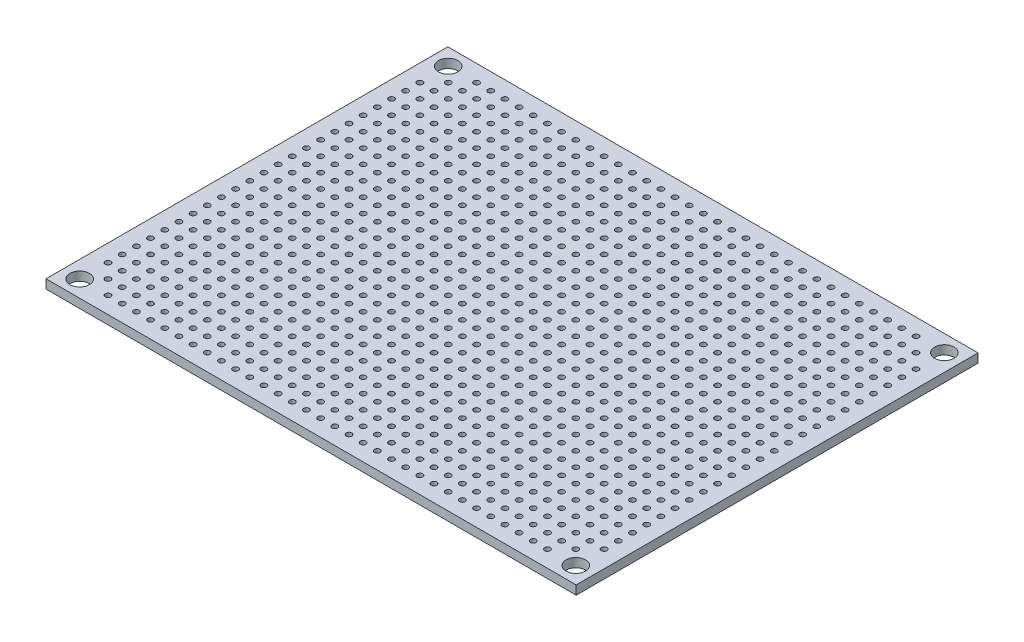
SolidWorks part; units mm, degrees
ref_plane "正面" through (0, 0, 0) normal (0, 0, 1) x (1, 0, 0)
ref_plane "平面" through (0, 0, 0) normal (0, 1, 0) x (1, 0, 0)
ref_plane "右側面" through (0, 0, 0) normal (1, 0, 0) x (0, 0, -1)
sketch "ｽｹｯﾁ1" plane through (0, 0, 0) normal (0, 1, 0) x (1, 0, 0)
  line L1 (0, 0) -> (95, 0)
  line L2 (0, 0) -> (0, 72)
  line L3 (0, 72) -> (95, 72)
  line L4 (95, 0) -> (95, 72)
  line L5 (3.05, 69.02) -> (91.95, 69.02) construction
  line L6 (3.05, 69.02) -> (3.05, 2.98) construction
  line L7 (3.05, 2.98) -> (91.95, 2.98) construction
  line L8 (91.95, 69.02) -> (91.95, 2.98) construction
  circle A0 centre (3.05, 69.02) radius 1.75
  circle A1 centre (91.95, 69.02) radius 1.75
  circle A2 centre (91.95, 2.98) radius 1.75
  circle A3 centre (3.05, 2.98) radius 1.75
  circle A5 centre (5.59, 69.02) radius 0.5
  circle A6 centre (8.13, 69.02) radius 0.5
  circle A7 centre (10.67, 69.02) radius 0.5
  circle A8 centre (13.21, 69.02) radius 0.5
  circle A9 centre (15.75, 69.02) radius 0.5
  circle A10 centre (18.29, 69.02) radius 0.5
  circle A11 centre (20.83, 69.02) radius 0.5
  circle A12 centre (23.37, 69.02) radius 0.5
  circle A13 centre (25.91, 69.02) radius 0.5
  circle A14 centre (28.45, 69.02) radius 0.5
  circle A15 centre (30.99, 69.02) radius 0.5
  circle A16 centre (33.53, 69.02) radius 0.5
  circle A17 centre (36.07, 69.02) radius 0.5
  circle A18 centre (38.61, 69.02) radius 0.5
  circle A19 centre (41.15, 69.02) radius 0.5
  circle A20 centre (43.69, 69.02) radius 0.5
  circle A21 centre (46.23, 69.02) radius 0.5
  circle A22 centre (48.77, 69.02) radius 0.5
  circle A23 centre (51.31, 69.02) radius 0.5
  circle A24 centre (53.85, 69.02) radius 0.5
  circle A25 centre (56.39, 69.02) radius 0.5
  circle A26 centre (58.93, 69.02) radius 0.5
  circle A27 centre (61.47, 69.02) radius 0.5
  circle A28 centre (64.01, 69.02) radius 0.5
  circle A29 centre (66.55, 69.02) radius 0.5
  circle A30 centre (69.09, 69.02) radius 0.5
  circle A31 centre (71.63, 69.02) radius 0.5
  circle A32 centre (74.17, 69.02) radius 0.5
  circle A33 centre (76.71, 69.02) radius 0.5
  circle A34 centre (79.25, 69.02) radius 0.5
  circle A35 centre (81.79, 69.02) radius 0.5
  circle A36 centre (84.33, 69.02) radius 0.5
  circle A37 centre (86.87, 69.02) radius 0.5
  circle A38 centre (89.41, 69.02) radius 0.5
  circle A39 centre (91.95, 69.02) radius 0.5
  circle A40 centre (3.05, 66.48) radius 0.5
  circle A41 centre (5.59, 66.48) radius 0.5
  circle A42 centre (8.13, 66.48) radius 0.5
  circle A43 centre (10.67, 66.48) radius 0.5
  circle A44 centre (13.21, 66.48) radius 0.5
  circle A45 centre (15.75, 66.48) radius 0.5
  circle A46 centre (18.29, 66.48) radius 0.5
  circle A47 centre (20.83, 66.48) radius 0.5
  circle A48 centre (23.37, 66.48) radius 0.5
  circle A49 centre (25.91, 66.48) radius 0.5
  circle A50 centre (28.45, 66.48) radius 0.5
  circle A51 centre (30.99, 66.48) radius 0.5
  circle A52 centre (33.53, 66.48) radius 0.5
  circle A53 centre (36.07, 66.48) radius 0.5
  circle A54 centre (38.61, 66.48) radius 0.5
  circle A55 centre (41.15, 66.48) radius 0.5
  circle A56 centre (43.69, 66.48) radius 0.5
  circle A57 centre (46.23, 66.48) radius 0.5
  circle A58 centre (48.77, 66.48) radius 0.5
  circle A59 centre (51.31, 66.48) radius 0.5
  circle A60 centre (53.85, 66.48) radius 0.5
  circle A61 centre (56.39, 66.48) radius 0.5
  circle A62 centre (58.93, 66.48) radius 0.5
  circle A63 centre (61.47, 66.48) radius 0.5
  circle A64 centre (64.01, 66.48) radius 0.5
  circle A65 centre (66.55, 66.48) radius 0.5
  circle A66 centre (69.09, 66.48) radius 0.5
  circle A67 centre (71.63, 66.48) radius 0.5
  circle A68 centre (74.17, 66.48) radius 0.5
  circle A69 centre (76.71, 66.48) radius 0.5
  circle A70 centre (79.25, 66.48) radius 0.5
  circle A71 centre (81.79, 66.48) radius 0.5
  circle A72 centre (84.33, 66.48) radius 0.5
  circle A73 centre (86.87, 66.48) radius 0.5
  circle A74 centre (89.41, 66.48) radius 0.5
  circle A75 centre (91.95, 66.48) radius 0.5
  circle A76 centre (3.05, 63.94) radius 0.5
  circle A77 centre (5.59, 63.94) radius 0.5
  circle A78 centre (8.13, 63.94) radius 0.5
  circle A79 centre (10.67, 63.94) radius 0.5
  circle A80 centre (13.21, 63.94) radius 0.5
  circle A81 centre (15.75, 63.94) radius 0.5
  circle A82 centre (18.29, 63.94) radius 0.5
  circle A83 centre (20.83, 63.94) radius 0.5
  circle A84 centre (23.37, 63.94) radius 0.5
  circle A85 centre (25.91, 63.94) radius 0.5
  circle A86 centre (28.45, 63.94) radius 0.5
  circle A87 centre (30.99, 63.94) radius 0.5
  circle A88 centre (33.53, 63.94) radius 0.5
  circle A89 centre (36.07, 63.94) radius 0.5
  circle A90 centre (38.61, 63.94) radius 0.5
  circle A91 centre (41.15, 63.94) radius 0.5
  circle A92 centre (43.69, 63.94) radius 0.5
  circle A93 centre (46.23, 63.94) radius 0.5
  circle A94 centre (48.77, 63.94) radius 0.5
  circle A95 centre (51.31, 63.94) radius 0.5
  circle A96 centre (53.85, 63.94) radius 0.5
  circle A97 centre (56.39, 63.94) radius 0.5
  circle A98 centre (58.93, 63.94) radius 0.5
  circle A99 centre (61.47, 63.94) radius 0.5
  circle A100 centre (64.01, 63.94) radius 0.5
  circle A101 centre (66.55, 63.94) radius 0.5
  circle A102 centre (69.09, 63.94) radius 0.5
  circle A103 centre (71.63, 63.94) radius 0.5
  circle A104 centre (74.17, 63.94) radius 0.5
  circle A105 centre (76.71, 63.94) radius 0.5
  circle A106 centre (79.25, 63.94) radius 0.5
  circle A107 centre (81.79, 63.94) radius 0.5
  circle A108 centre (84.33, 63.94) radius 0.5
  circle A109 centre (86.87, 63.94) radius 0.5
  circle A110 centre (89.41, 63.94) radius 0.5
  circle A111 centre (91.95, 63.94) radius 0.5
  circle A112 centre (3.05, 61.4) radius 0.5
  circle A113 centre (5.59, 61.4) radius 0.5
  circle A114 centre (8.13, 61.4) radius 0.5
  circle A115 centre (10.67, 61.4) radius 0.5
  circle A116 centre (13.21, 61.4) radius 0.5
  circle A117 centre (15.75, 61.4) radius 0.5
  circle A118 centre (18.29, 61.4) radius 0.5
  circle A119 centre (20.83, 61.4) radius 0.5
  circle A120 centre (23.37, 61.4) radius 0.5
  circle A121 centre (25.91, 61.4) radius 0.5
  circle A122 centre (28.45, 61.4) radius 0.5
  circle A123 centre (30.99, 61.4) radius 0.5
  circle A124 centre (33.53, 61.4) radius 0.5
  circle A125 centre (36.07, 61.4) radius 0.5
  circle A126 centre (38.61, 61.4) radius 0.5
  circle A127 centre (41.15, 61.4) radius 0.5
  circle A128 centre (43.69, 61.4) radius 0.5
  circle A129 centre (46.23, 61.4) radius 0.5
  circle A130 centre (48.77, 61.4) radius 0.5
  circle A131 centre (51.31, 61.4) radius 0.5
  circle A132 centre (53.85, 61.4) radius 0.5
  circle A133 centre (56.39, 61.4) radius 0.5
  circle A134 centre (58.93, 61.4) radius 0.5
  circle A135 centre (61.47, 61.4) radius 0.5
  circle A136 centre (64.01, 61.4) radius 0.5
  circle A137 centre (66.55, 61.4) radius 0.5
  circle A138 centre (69.09, 61.4) radius 0.5
  circle A139 centre (71.63, 61.4) radius 0.5
  circle A140 centre (74.17, 61.4) radius 0.5
  circle A141 centre (76.71, 61.4) radius 0.5
  circle A142 centre (79.25, 61.4) radius 0.5
  circle A143 centre (81.79, 61.4) radius 0.5
  circle A144 centre (84.33, 61.4) radius 0.5
  circle A145 centre (86.87, 61.4) radius 0.5
  circle A146 centre (89.41, 61.4) radius 0.5
  circle A147 centre (91.95, 61.4) radius 0.5
  circle A148 centre (3.05, 58.86) radius 0.5
  circle A149 centre (5.59, 58.86) radius 0.5
  circle A150 centre (8.13, 58.86) radius 0.5
  circle A151 centre (10.67, 58.86) radius 0.5
  circle A152 centre (13.21, 58.86) radius 0.5
  circle A153 centre (15.75, 58.86) radius 0.5
  circle A154 centre (18.29, 58.86) radius 0.5
  circle A155 centre (20.83, 58.86) radius 0.5
  circle A156 centre (23.37, 58.86) radius 0.5
  circle A157 centre (25.91, 58.86) radius 0.5
  circle A158 centre (28.45, 58.86) radius 0.5
  circle A159 centre (30.99, 58.86) radius 0.5
  circle A160 centre (33.53, 58.86) radius 0.5
  circle A161 centre (36.07, 58.86) radius 0.5
  circle A162 centre (38.61, 58.86) radius 0.5
  circle A163 centre (41.15, 58.86) radius 0.5
  circle A164 centre (43.69, 58.86) radius 0.5
  circle A165 centre (46.23, 58.86) radius 0.5
  circle A166 centre (48.77, 58.86) radius 0.5
  circle A167 centre (51.31, 58.86) radius 0.5
  circle A168 centre (53.85, 58.86) radius 0.5
  circle A169 centre (56.39, 58.86) radius 0.5
  circle A170 centre (58.93, 58.86) radius 0.5
  circle A171 centre (61.47, 58.86) radius 0.5
  circle A172 centre (64.01, 58.86) radius 0.5
  circle A173 centre (66.55, 58.86) radius 0.5
  circle A174 centre (69.09, 58.86) radius 0.5
  circle A175 centre (71.63, 58.86) radius 0.5
  circle A176 centre (74.17, 58.86) radius 0.5
  circle A177 centre (76.71, 58.86) radius 0.5
  circle A178 centre (79.25, 58.86) radius 0.5
  circle A179 centre (81.79, 58.86) radius 0.5
  circle A180 centre (84.33, 58.86) radius 0.5
  circle A181 centre (86.87, 58.86) radius 0.5
  circle A182 centre (89.41, 58.86) radius 0.5
  circle A183 centre (91.95, 58.86) radius 0.5
  circle A184 centre (3.05, 56.32) radius 0.5
  circle A185 centre (5.59, 56.32) radius 0.5
  circle A186 centre (8.13, 56.32) radius 0.5
  circle A187 centre (10.67, 56.32) radius 0.5
  circle A188 centre (13.21, 56.32) radius 0.5
  circle A189 centre (15.75, 56.32) radius 0.5
  circle A190 centre (18.29, 56.32) radius 0.5
  circle A191 centre (20.83, 56.32) radius 0.5
  circle A192 centre (23.37, 56.32) radius 0.5
  circle A193 centre (25.91, 56.32) radius 0.5
  circle A194 centre (28.45, 56.32) radius 0.5
  circle A195 centre (30.99, 56.32) radius 0.5
  circle A196 centre (33.53, 56.32) radius 0.5
  circle A197 centre (36.07, 56.32) radius 0.5
  circle A198 centre (38.61, 56.32) radius 0.5
  circle A199 centre (41.15, 56.32) radius 0.5
  circle A200 centre (43.69, 56.32) radius 0.5
  circle A201 centre (46.23, 56.32) radius 0.5
  circle A202 centre (48.77, 56.32) radius 0.5
  circle A203 centre (51.31, 56.32) radius 0.5
  circle A204 centre (53.85, 56.32) radius 0.5
  circle A205 centre (56.39, 56.32) radius 0.5
  circle A206 centre (58.93, 56.32) radius 0.5
  circle A207 centre (61.47, 56.32) radius 0.5
  circle A208 centre (64.01, 56.32) radius 0.5
  circle A209 centre (66.55, 56.32) radius 0.5
  circle A210 centre (69.09, 56.32) radius 0.5
  circle A211 centre (71.63, 56.32) radius 0.5
  circle A212 centre (74.17, 56.32) radius 0.5
  circle A213 centre (76.71, 56.32) radius 0.5
  circle A214 centre (79.25, 56.32) radius 0.5
  circle A215 centre (81.79, 56.32) radius 0.5
  circle A216 centre (84.33, 56.32) radius 0.5
  circle A217 centre (86.87, 56.32) radius 0.5
  circle A218 centre (89.41, 56.32) radius 0.5
  circle A219 centre (91.95, 56.32) radius 0.5
  circle A220 centre (3.05, 53.78) radius 0.5
  circle A221 centre (5.59, 53.78) radius 0.5
  circle A222 centre (8.13, 53.78) radius 0.5
  circle A223 centre (10.67, 53.78) radius 0.5
  circle A224 centre (13.21, 53.78) radius 0.5
  circle A225 centre (15.75, 53.78) radius 0.5
  circle A226 centre (18.29, 53.78) radius 0.5
  circle A227 centre (20.83, 53.78) radius 0.5
  circle A228 centre (23.37, 53.78) radius 0.5
  circle A229 centre (25.91, 53.78) radius 0.5
  circle A230 centre (28.45, 53.78) radius 0.5
  circle A231 centre (30.99, 53.78) radius 0.5
  circle A232 centre (33.53, 53.78) radius 0.5
  circle A233 centre (36.07, 53.78) radius 0.5
  circle A234 centre (38.61, 53.78) radius 0.5
  circle A235 centre (41.15, 53.78) radius 0.5
  circle A236 centre (43.69, 53.78) radius 0.5
  circle A237 centre (46.23, 53.78) radius 0.5
  circle A238 centre (48.77, 53.78) radius 0.5
  circle A239 centre (51.31, 53.78) radius 0.5
  circle A240 centre (53.85, 53.78) radius 0.5
  circle A241 centre (56.39, 53.78) radius 0.5
  circle A242 centre (58.93, 53.78) radius 0.5
  circle A243 centre (61.47, 53.78) radius 0.5
  circle A244 centre (64.01, 53.78) radius 0.5
  circle A245 centre (66.55, 53.78) radius 0.5
  circle A246 centre (69.09, 53.78) radius 0.5
  circle A247 centre (71.63, 53.78) radius 0.5
  circle A248 centre (74.17, 53.78) radius 0.5
  circle A249 centre (76.71, 53.78) radius 0.5
  circle A250 centre (79.25, 53.78) radius 0.5
  circle A251 centre (81.79, 53.78) radius 0.5
  circle A252 centre (84.33, 53.78) radius 0.5
  circle A253 centre (86.87, 53.78) radius 0.5
  circle A254 centre (89.41, 53.78) radius 0.5
  circle A255 centre (91.95, 53.78) radius 0.5
  circle A256 centre (3.05, 51.24) radius 0.5
  circle A257 centre (5.59, 51.24) radius 0.5
  circle A258 centre (8.13, 51.24) radius 0.5
  circle A259 centre (10.67, 51.24) radius 0.5
  circle A260 centre (13.21, 51.24) radius 0.5
  circle A261 centre (15.75, 51.24) radius 0.5
  circle A262 centre (18.29, 51.24) radius 0.5
  circle A263 centre (20.83, 51.24) radius 0.5
  circle A264 centre (23.37, 51.24) radius 0.5
  circle A265 centre (25.91, 51.24) radius 0.5
  circle A266 centre (28.45, 51.24) radius 0.5
  circle A267 centre (30.99, 51.24) radius 0.5
  circle A268 centre (33.53, 51.24) radius 0.5
  circle A269 centre (36.07, 51.24) radius 0.5
  circle A270 centre (38.61, 51.24) radius 0.5
  circle A271 centre (41.15, 51.24) radius 0.5
  circle A272 centre (43.69, 51.24) radius 0.5
  circle A273 centre (46.23, 51.24) radius 0.5
  circle A274 centre (48.77, 51.24) radius 0.5
  circle A275 centre (51.31, 51.24) radius 0.5
  circle A276 centre (53.85, 51.24) radius 0.5
  circle A277 centre (56.39, 51.24) radius 0.5
  circle A278 centre (58.93, 51.24) radius 0.5
  circle A279 centre (61.47, 51.24) radius 0.5
  circle A280 centre (64.01, 51.24) radius 0.5
  circle A281 centre (66.55, 51.24) radius 0.5
  circle A282 centre (69.09, 51.24) radius 0.5
  circle A283 centre (71.63, 51.24) radius 0.5
  circle A284 centre (74.17, 51.24) radius 0.5
  circle A285 centre (76.71, 51.24) radius 0.5
  circle A286 centre (79.25, 51.24) radius 0.5
  circle A287 centre (81.79, 51.24) radius 0.5
  circle A288 centre (84.33, 51.24) radius 0.5
  circle A289 centre (86.87, 51.24) radius 0.5
  circle A290 centre (89.41, 51.24) radius 0.5
  circle A291 centre (91.95, 51.24) radius 0.5
  circle A292 centre (3.05, 48.7) radius 0.5
  circle A293 centre (5.59, 48.7) radius 0.5
  circle A294 centre (8.13, 48.7) radius 0.5
  circle A295 centre (10.67, 48.7) radius 0.5
  circle A296 centre (13.21, 48.7) radius 0.5
  circle A297 centre (15.75, 48.7) radius 0.5
  circle A298 centre (18.29, 48.7) radius 0.5
  circle A299 centre (20.83, 48.7) radius 0.5
  circle A300 centre (23.37, 48.7) radius 0.5
  circle A301 centre (25.91, 48.7) radius 0.5
  circle A302 centre (28.45, 48.7) radius 0.5
  circle A303 centre (30.99, 48.7) radius 0.5
  circle A304 centre (33.53, 48.7) radius 0.5
  circle A305 centre (36.07, 48.7) radius 0.5
  circle A306 centre (38.61, 48.7) radius 0.5
  circle A307 centre (41.15, 48.7) radius 0.5
  circle A308 centre (43.69, 48.7) radius 0.5
  circle A309 centre (46.23, 48.7) radius 0.5
  circle A310 centre (48.77, 48.7) radius 0.5
  circle A311 centre (51.31, 48.7) radius 0.5
  circle A312 centre (53.85, 48.7) radius 0.5
  circle A313 centre (56.39, 48.7) radius 0.5
  circle A314 centre (58.93, 48.7) radius 0.5
  circle A315 centre (61.47, 48.7) radius 0.5
  circle A316 centre (64.01, 48.7) radius 0.5
  circle A317 centre (66.55, 48.7) radius 0.5
  circle A318 centre (69.09, 48.7) radius 0.5
  circle A319 centre (71.63, 48.7) radius 0.5
  circle A320 centre (74.17, 48.7) radius 0.5
  circle A321 centre (76.71, 48.7) radius 0.5
  circle A322 centre (79.25, 48.7) radius 0.5
  circle A323 centre (81.79, 48.7) radius 0.5
  circle A324 centre (84.33, 48.7) radius 0.5
  circle A325 centre (86.87, 48.7) radius 0.5
  circle A326 centre (89.41, 48.7) radius 0.5
  circle A327 centre (91.95, 48.7) radius 0.5
  circle A328 centre (3.05, 46.16) radius 0.5
  circle A329 centre (5.59, 46.16) radius 0.5
  circle A330 centre (8.13, 46.16) radius 0.5
  circle A331 centre (10.67, 46.16) radius 0.5
  circle A332 centre (13.21, 46.16) radius 0.5
  circle A333 centre (15.75, 46.16) radius 0.5
  circle A334 centre (18.29, 46.16) radius 0.5
  circle A335 centre (20.83, 46.16) radius 0.5
  circle A336 centre (23.37, 46.16) radius 0.5
  circle A337 centre (25.91, 46.16) radius 0.5
  circle A338 centre (28.45, 46.16) radius 0.5
  circle A339 centre (30.99, 46.16) radius 0.5
  circle A340 centre (33.53, 46.16) radius 0.5
  circle A341 centre (36.07, 46.16) radius 0.5
  circle A342 centre (38.61, 46.16) radius 0.5
  circle A343 centre (41.15, 46.16) radius 0.5
  circle A344 centre (43.69, 46.16) radius 0.5
  circle A345 centre (46.23, 46.16) radius 0.5
  circle A346 centre (48.77, 46.16) radius 0.5
  circle A347 centre (51.31, 46.16) radius 0.5
  circle A348 centre (53.85, 46.16) radius 0.5
  circle A349 centre (56.39, 46.16) radius 0.5
  circle A350 centre (58.93, 46.16) radius 0.5
  circle A351 centre (61.47, 46.16) radius 0.5
  circle A352 centre (64.01, 46.16) radius 0.5
  circle A353 centre (66.55, 46.16) radius 0.5
  circle A354 centre (69.09, 46.16) radius 0.5
  circle A355 centre (71.63, 46.16) radius 0.5
  circle A356 centre (74.17, 46.16) radius 0.5
  circle A357 centre (76.71, 46.16) radius 0.5
  circle A358 centre (79.25, 46.16) radius 0.5
  circle A359 centre (81.79, 46.16) radius 0.5
  circle A360 centre (84.33, 46.16) radius 0.5
  circle A361 centre (86.87, 46.16) radius 0.5
  circle A362 centre (89.41, 46.16) radius 0.5
  circle A363 centre (91.95, 46.16) radius 0.5
  circle A364 centre (3.05, 43.62) radius 0.5
  circle A365 centre (5.59, 43.62) radius 0.5
  circle A366 centre (8.13, 43.62) radius 0.5
  circle A367 centre (10.67, 43.62) radius 0.5
  circle A368 centre (13.21, 43.62) radius 0.5
  circle A369 centre (15.75, 43.62) radius 0.5
  circle A370 centre (18.29, 43.62) radius 0.5
  circle A371 centre (20.83, 43.62) radius 0.5
  circle A372 centre (23.37, 43.62) radius 0.5
  circle A373 centre (25.91, 43.62) radius 0.5
  circle A374 centre (28.45, 43.62) radius 0.5
  circle A375 centre (30.99, 43.62) radius 0.5
  circle A376 centre (33.53, 43.62) radius 0.5
  circle A377 centre (36.07, 43.62) radius 0.5
  circle A378 centre (38.61, 43.62) radius 0.5
  circle A379 centre (41.15, 43.62) radius 0.5
  circle A380 centre (43.69, 43.62) radius 0.5
  circle A381 centre (46.23, 43.62) radius 0.5
  circle A382 centre (48.77, 43.62) radius 0.5
  circle A383 centre (51.31, 43.62) radius 0.5
  circle A384 centre (53.85, 43.62) radius 0.5
  circle A385 centre (56.39, 43.62) radius 0.5
  circle A386 centre (58.93, 43.62) radius 0.5
  circle A387 centre (61.47, 43.62) radius 0.5
  circle A388 centre (64.01, 43.62) radius 0.5
  circle A389 centre (66.55, 43.62) radius 0.5
  circle A390 centre (69.09, 43.62) radius 0.5
  circle A391 centre (71.63, 43.62) radius 0.5
  circle A392 centre (74.17, 43.62) radius 0.5
  circle A393 centre (76.71, 43.62) radius 0.5
  circle A394 centre (79.25, 43.62) radius 0.5
  circle A395 centre (81.79, 43.62) radius 0.5
  circle A396 centre (84.33, 43.62) radius 0.5
  circle A397 centre (86.87, 43.62) radius 0.5
  circle A398 centre (89.41, 43.62) radius 0.5
  circle A399 centre (91.95, 43.62) radius 0.5
  circle A400 centre (3.05, 41.08) radius 0.5
  circle A401 centre (5.59, 41.08) radius 0.5
  circle A402 centre (8.13, 41.08) radius 0.5
  circle A403 centre (10.67, 41.08) radius 0.5
  circle A404 centre (13.21, 41.08) radius 0.5
  circle A405 centre (15.75, 41.08) radius 0.5
  circle A406 centre (18.29, 41.08) radius 0.5
  circle A407 centre (20.83, 41.08) radius 0.5
  circle A408 centre (23.37, 41.08) radius 0.5
  circle A409 centre (25.91, 41.08) radius 0.5
  circle A410 centre (28.45, 41.08) radius 0.5
  circle A411 centre (30.99, 41.08) radius 0.5
  circle A412 centre (33.53, 41.08) radius 0.5
  circle A413 centre (36.07, 41.08) radius 0.5
  circle A414 centre (38.61, 41.08) radius 0.5
  circle A415 centre (41.15, 41.08) radius 0.5
  circle A416 centre (43.69, 41.08) radius 0.5
  circle A417 centre (46.23, 41.08) radius 0.5
  circle A418 centre (48.77, 41.08) radius 0.5
  circle A419 centre (51.31, 41.08) radius 0.5
  circle A420 centre (53.85, 41.08) radius 0.5
  circle A421 centre (56.39, 41.08) radius 0.5
  circle A422 centre (58.93, 41.08) radius 0.5
  circle A423 centre (61.47, 41.08) radius 0.5
  circle A424 centre (64.01, 41.08) radius 0.5
  circle A425 centre (66.55, 41.08) radius 0.5
  circle A426 centre (69.09, 41.08) radius 0.5
  circle A427 centre (71.63, 41.08) radius 0.5
  circle A428 centre (74.17, 41.08) radius 0.5
  circle A429 centre (76.71, 41.08) radius 0.5
  circle A430 centre (79.25, 41.08) radius 0.5
  circle A431 centre (81.79, 41.08) radius 0.5
  circle A432 centre (84.33, 41.08) radius 0.5
  circle A433 centre (86.87, 41.08) radius 0.5
  circle A434 centre (89.41, 41.08) radius 0.5
  circle A435 centre (91.95, 41.08) radius 0.5
  circle A436 centre (3.05, 38.54) radius 0.5
  circle A437 centre (5.59, 38.54) radius 0.5
  circle A438 centre (8.13, 38.54) radius 0.5
  circle A439 centre (10.67, 38.54) radius 0.5
  circle A440 centre (13.21, 38.54) radius 0.5
  circle A441 centre (15.75, 38.54) radius 0.5
  circle A442 centre (18.29, 38.54) radius 0.5
  circle A443 centre (20.83, 38.54) radius 0.5
  circle A444 centre (23.37, 38.54) radius 0.5
  circle A445 centre (25.91, 38.54) radius 0.5
  circle A446 centre (28.45, 38.54) radius 0.5
  circle A447 centre (30.99, 38.54) radius 0.5
  circle A448 centre (33.53, 38.54) radius 0.5
  circle A449 centre (36.07, 38.54) radius 0.5
  circle A450 centre (38.61, 38.54) radius 0.5
  circle A451 centre (41.15, 38.54) radius 0.5
  circle A452 centre (43.69, 38.54) radius 0.5
  circle A453 centre (46.23, 38.54) radius 0.5
  circle A454 centre (48.77, 38.54) radius 0.5
  circle A455 centre (51.31, 38.54) radius 0.5
  circle A456 centre (53.85, 38.54) radius 0.5
  circle A457 centre (56.39, 38.54) radius 0.5
  circle A458 centre (58.93, 38.54) radius 0.5
  circle A459 centre (61.47, 38.54) radius 0.5
  circle A460 centre (64.01, 38.54) radius 0.5
  circle A461 centre (66.55, 38.54) radius 0.5
  circle A462 centre (69.09, 38.54) radius 0.5
  circle A463 centre (71.63, 38.54) radius 0.5
  circle A464 centre (74.17, 38.54) radius 0.5
  circle A465 centre (76.71, 38.54) radius 0.5
  circle A466 centre (79.25, 38.54) radius 0.5
  circle A467 centre (81.79, 38.54) radius 0.5
  circle A468 centre (84.33, 38.54) radius 0.5
  circle A469 centre (86.87, 38.54) radius 0.5
  circle A470 centre (89.41, 38.54) radius 0.5
  circle A471 centre (91.95, 38.54) radius 0.5
  circle A472 centre (3.05, 36) radius 0.5
  circle A473 centre (5.59, 36) radius 0.5
  circle A474 centre (8.13, 36) radius 0.5
  circle A475 centre (10.67, 36) radius 0.5
  circle A476 centre (13.21, 36) radius 0.5
  circle A477 centre (15.75, 36) radius 0.5
  circle A478 centre (18.29, 36) radius 0.5
  circle A479 centre (20.83, 36) radius 0.5
  circle A480 centre (23.37, 36) radius 0.5
  circle A481 centre (25.91, 36) radius 0.5
  circle A482 centre (28.45, 36) radius 0.5
  circle A483 centre (30.99, 36) radius 0.5
  circle A484 centre (33.53, 36) radius 0.5
  circle A485 centre (36.07, 36) radius 0.5
  circle A486 centre (38.61, 36) radius 0.5
  circle A487 centre (41.15, 36) radius 0.5
  circle A488 centre (43.69, 36) radius 0.5
  circle A489 centre (46.23, 36) radius 0.5
  circle A490 centre (48.77, 36) radius 0.5
  circle A491 centre (51.31, 36) radius 0.5
  circle A492 centre (53.85, 36) radius 0.5
  circle A493 centre (56.39, 36) radius 0.5
  circle A494 centre (58.93, 36) radius 0.5
  circle A495 centre (61.47, 36) radius 0.5
  circle A496 centre (64.01, 36) radius 0.5
  circle A497 centre (66.55, 36) radius 0.5
  circle A498 centre (69.09, 36) radius 0.5
  circle A499 centre (71.63, 36) radius 0.5
  circle A500 centre (74.17, 36) radius 0.5
  circle A501 centre (76.71, 36) radius 0.5
  circle A502 centre (79.25, 36) radius 0.5
  circle A503 centre (81.79, 36) radius 0.5
  circle A504 centre (84.33, 36) radius 0.5
  circle A505 centre (86.87, 36) radius 0.5
  circle A506 centre (89.41, 36) radius 0.5
  circle A507 centre (91.95, 36) radius 0.5
  circle A508 centre (3.05, 33.46) radius 0.5
  circle A509 centre (5.59, 33.46) radius 0.5
  circle A510 centre (8.13, 33.46) radius 0.5
  circle A511 centre (10.67, 33.46) radius 0.5
  circle A512 centre (13.21, 33.46) radius 0.5
  circle A513 centre (15.75, 33.46) radius 0.5
  circle A514 centre (18.29, 33.46) radius 0.5
  circle A515 centre (20.83, 33.46) radius 0.5
  circle A516 centre (23.37, 33.46) radius 0.5
  circle A517 centre (25.91, 33.46) radius 0.5
  circle A518 centre (28.45, 33.46) radius 0.5
  circle A519 centre (30.99, 33.46) radius 0.5
  circle A520 centre (33.53, 33.46) radius 0.5
  circle A521 centre (36.07, 33.46) radius 0.5
  circle A522 centre (38.61, 33.46) radius 0.5
  circle A523 centre (41.15, 33.46) radius 0.5
  circle A524 centre (43.69, 33.46) radius 0.5
  circle A525 centre (46.23, 33.46) radius 0.5
  circle A526 centre (48.77, 33.46) radius 0.5
  circle A527 centre (51.31, 33.46) radius 0.5
  circle A528 centre (53.85, 33.46) radius 0.5
  circle A529 centre (56.39, 33.46) radius 0.5
  circle A530 centre (58.93, 33.46) radius 0.5
  circle A531 centre (61.47, 33.46) radius 0.5
  circle A532 centre (64.01, 33.46) radius 0.5
  circle A533 centre (66.55, 33.46) radius 0.5
  circle A534 centre (69.09, 33.46) radius 0.5
  circle A535 centre (71.63, 33.46) radius 0.5
  circle A536 centre (74.17, 33.46) radius 0.5
  circle A537 centre (76.71, 33.46) radius 0.5
  circle A538 centre (79.25, 33.46) radius 0.5
  circle A539 centre (81.79, 33.46) radius 0.5
  circle A540 centre (84.33, 33.46) radius 0.5
  circle A541 centre (86.87, 33.46) radius 0.5
  circle A542 centre (89.41, 33.46) radius 0.5
  circle A543 centre (91.95, 33.46) radius 0.5
  circle A544 centre (3.05, 30.92) radius 0.5
  circle A545 centre (5.59, 30.92) radius 0.5
  circle A546 centre (8.13, 30.92) radius 0.5
  circle A547 centre (10.67, 30.92) radius 0.5
  circle A548 centre (13.21, 30.92) radius 0.5
  circle A549 centre (15.75, 30.92) radius 0.5
  circle A550 centre (18.29, 30.92) radius 0.5
  circle A551 centre (20.83, 30.92) radius 0.5
  circle A552 centre (23.37, 30.92) radius 0.5
  circle A553 centre (25.91, 30.92) radius 0.5
  circle A554 centre (28.45, 30.92) radius 0.5
  circle A555 centre (30.99, 30.92) radius 0.5
  circle A556 centre (33.53, 30.92) radius 0.5
  circle A557 centre (36.07, 30.92) radius 0.5
  circle A558 centre (38.61, 30.92) radius 0.5
  circle A559 centre (41.15, 30.92) radius 0.5
  circle A560 centre (43.69, 30.92) radius 0.5
  circle A561 centre (46.23, 30.92) radius 0.5
  circle A562 centre (48.77, 30.92) radius 0.5
  circle A563 centre (51.31, 30.92) radius 0.5
  circle A564 centre (53.85, 30.92) radius 0.5
  circle A565 centre (56.39, 30.92) radius 0.5
  circle A566 centre (58.93, 30.92) radius 0.5
  circle A567 centre (61.47, 30.92) radius 0.5
  circle A568 centre (64.01, 30.92) radius 0.5
  circle A569 centre (66.55, 30.92) radius 0.5
  circle A570 centre (69.09, 30.92) radius 0.5
  circle A571 centre (71.63, 30.92) radius 0.5
  circle A572 centre (74.17, 30.92) radius 0.5
  circle A573 centre (76.71, 30.92) radius 0.5
  circle A574 centre (79.25, 30.92) radius 0.5
  circle A575 centre (81.79, 30.92) radius 0.5
  circle A576 centre (84.33, 30.92) radius 0.5
  circle A577 centre (86.87, 30.92) radius 0.5
  circle A578 centre (89.41, 30.92) radius 0.5
  circle A579 centre (91.95, 30.92) radius 0.5
  circle A580 centre (3.05, 28.38) radius 0.5
  circle A581 centre (5.59, 28.38) radius 0.5
  circle A582 centre (8.13, 28.38) radius 0.5
  circle A583 centre (10.67, 28.38) radius 0.5
  circle A584 centre (13.21, 28.38) radius 0.5
  circle A585 centre (15.75, 28.38) radius 0.5
  circle A586 centre (18.29, 28.38) radius 0.5
  circle A587 centre (20.83, 28.38) radius 0.5
  circle A588 centre (23.37, 28.38) radius 0.5
  circle A589 centre (25.91, 28.38) radius 0.5
  circle A590 centre (28.45, 28.38) radius 0.5
  circle A591 centre (30.99, 28.38) radius 0.5
  circle A592 centre (33.53, 28.38) radius 0.5
  circle A593 centre (36.07, 28.38) radius 0.5
  circle A594 centre (38.61, 28.38) radius 0.5
  circle A595 centre (41.15, 28.38) radius 0.5
  circle A596 centre (43.69, 28.38) radius 0.5
  circle A597 centre (46.23, 28.38) radius 0.5
  circle A598 centre (48.77, 28.38) radius 0.5
  circle A599 centre (51.31, 28.38) radius 0.5
  circle A600 centre (53.85, 28.38) radius 0.5
  circle A601 centre (56.39, 28.38) radius 0.5
  circle A602 centre (58.93, 28.38) radius 0.5
  circle A603 centre (61.47, 28.38) radius 0.5
  circle A604 centre (64.01, 28.38) radius 0.5
  circle A605 centre (66.55, 28.38) radius 0.5
  circle A606 centre (69.09, 28.38) radius 0.5
  circle A607 centre (71.63, 28.38) radius 0.5
  circle A608 centre (74.17, 28.38) radius 0.5
  circle A609 centre (76.71, 28.38) radius 0.5
  circle A610 centre (79.25, 28.38) radius 0.5
  circle A611 centre (81.79, 28.38) radius 0.5
  circle A612 centre (84.33, 28.38) radius 0.5
  circle A613 centre (86.87, 28.38) radius 0.5
  circle A614 centre (89.41, 28.38) radius 0.5
  circle A615 centre (91.95, 28.38) radius 0.5
  circle A616 centre (3.05, 25.84) radius 0.5
  circle A617 centre (5.59, 25.84) radius 0.5
  circle A618 centre (8.13, 25.84) radius 0.5
  circle A619 centre (10.67, 25.84) radius 0.5
  circle A620 centre (13.21, 25.84) radius 0.5
  circle A621 centre (15.75, 25.84) radius 0.5
  circle A622 centre (18.29, 25.84) radius 0.5
  circle A623 centre (20.83, 25.84) radius 0.5
  circle A624 centre (23.37, 25.84) radius 0.5
  circle A625 centre (25.91, 25.84) radius 0.5
  circle A626 centre (28.45, 25.84) radius 0.5
  circle A627 centre (30.99, 25.84) radius 0.5
  circle A628 centre (33.53, 25.84) radius 0.5
  circle A629 centre (36.07, 25.84) radius 0.5
  circle A630 centre (38.61, 25.84) radius 0.5
  circle A631 centre (41.15, 25.84) radius 0.5
  circle A632 centre (43.69, 25.84) radius 0.5
  circle A633 centre (46.23, 25.84) radius 0.5
  circle A634 centre (48.77, 25.84) radius 0.5
  circle A635 centre (51.31, 25.84) radius 0.5
  circle A636 centre (53.85, 25.84) radius 0.5
  circle A637 centre (56.39, 25.84) radius 0.5
  circle A638 centre (58.93, 25.84) radius 0.5
  circle A639 centre (61.47, 25.84) radius 0.5
  circle A640 centre (64.01, 25.84) radius 0.5
  circle A641 centre (66.55, 25.84) radius 0.5
  circle A642 centre (69.09, 25.84) radius 0.5
  circle A643 centre (71.63, 25.84) radius 0.5
  circle A644 centre (74.17, 25.84) radius 0.5
  circle A645 centre (76.71, 25.84) radius 0.5
  circle A646 centre (79.25, 25.84) radius 0.5
  circle A647 centre (81.79, 25.84) radius 0.5
  circle A648 centre (84.33, 25.84) radius 0.5
  circle A649 centre (86.87, 25.84) radius 0.5
  circle A650 centre (89.41, 25.84) radius 0.5
  circle A651 centre (91.95, 25.84) radius 0.5
  circle A652 centre (3.05, 23.3) radius 0.5
  circle A653 centre (5.59, 23.3) radius 0.5
  circle A654 centre (8.13, 23.3) radius 0.5
  circle A655 centre (10.67, 23.3) radius 0.5
  circle A656 centre (13.21, 23.3) radius 0.5
  circle A657 centre (15.75, 23.3) radius 0.5
  circle A658 centre (18.29, 23.3) radius 0.5
  circle A659 centre (20.83, 23.3) radius 0.5
  circle A660 centre (23.37, 23.3) radius 0.5
  circle A661 centre (25.91, 23.3) radius 0.5
  circle A662 centre (28.45, 23.3) radius 0.5
  circle A663 centre (30.99, 23.3) radius 0.5
  circle A664 centre (33.53, 23.3) radius 0.5
  circle A665 centre (36.07, 23.3) radius 0.5
  circle A666 centre (38.61, 23.3) radius 0.5
  circle A667 centre (41.15, 23.3) radius 0.5
  circle A668 centre (43.69, 23.3) radius 0.5
  circle A669 centre (46.23, 23.3) radius 0.5
  circle A670 centre (48.77, 23.3) radius 0.5
  circle A671 centre (51.31, 23.3) radius 0.5
  circle A672 centre (53.85, 23.3) radius 0.5
  circle A673 centre (56.39, 23.3) radius 0.5
  circle A674 centre (58.93, 23.3) radius 0.5
  circle A675 centre (61.47, 23.3) radius 0.5
  circle A676 centre (64.01, 23.3) radius 0.5
  circle A677 centre (66.55, 23.3) radius 0.5
  circle A678 centre (69.09, 23.3) radius 0.5
  circle A679 centre (71.63, 23.3) radius 0.5
  circle A680 centre (74.17, 23.3) radius 0.5
  circle A681 centre (76.71, 23.3) radius 0.5
  circle A682 centre (79.25, 23.3) radius 0.5
  circle A683 centre (81.79, 23.3) radius 0.5
  circle A684 centre (84.33, 23.3) radius 0.5
  circle A685 centre (86.87, 23.3) radius 0.5
  circle A686 centre (89.41, 23.3) radius 0.5
  circle A687 centre (91.95, 23.3) radius 0.5
  circle A688 centre (3.05, 20.76) radius 0.5
  circle A689 centre (5.59, 20.76) radius 0.5
  circle A690 centre (8.13, 20.76) radius 0.5
  circle A691 centre (10.67, 20.76) radius 0.5
  circle A692 centre (13.21, 20.76) radius 0.5
  circle A693 centre (15.75, 20.76) radius 0.5
  circle A694 centre (18.29, 20.76) radius 0.5
  circle A695 centre (20.83, 20.76) radius 0.5
  circle A696 centre (23.37, 20.76) radius 0.5
  circle A697 centre (25.91, 20.76) radius 0.5
  circle A698 centre (28.45, 20.76) radius 0.5
  circle A699 centre (30.99, 20.76) radius 0.5
  circle A700 centre (33.53, 20.76) radius 0.5
  circle A701 centre (36.07, 20.76) radius 0.5
  circle A702 centre (38.61, 20.76) radius 0.5
  circle A703 centre (41.15, 20.76) radius 0.5
  circle A704 centre (43.69, 20.76) radius 0.5
  circle A705 centre (46.23, 20.76) radius 0.5
  circle A706 centre (48.77, 20.76) radius 0.5
  circle A707 centre (51.31, 20.76) radius 0.5
  circle A708 centre (53.85, 20.76) radius 0.5
  circle A709 centre (56.39, 20.76) radius 0.5
  circle A710 centre (58.93, 20.76) radius 0.5
  circle A711 centre (61.47, 20.76) radius 0.5
  circle A712 centre (64.01, 20.76) radius 0.5
  circle A713 centre (66.55, 20.76) radius 0.5
  circle A714 centre (69.09, 20.76) radius 0.5
  circle A715 centre (71.63, 20.76) radius 0.5
  circle A716 centre (74.17, 20.76) radius 0.5
  circle A717 centre (76.71, 20.76) radius 0.5
  circle A718 centre (79.25, 20.76) radius 0.5
  circle A719 centre (81.79, 20.76) radius 0.5
  circle A720 centre (84.33, 20.76) radius 0.5
  circle A721 centre (86.87, 20.76) radius 0.5
  circle A722 centre (89.41, 20.76) radius 0.5
  circle A723 centre (91.95, 20.76) radius 0.5
  circle A724 centre (3.05, 18.22) radius 0.5
  circle A725 centre (5.59, 18.22) radius 0.5
  circle A726 centre (8.13, 18.22) radius 0.5
  circle A727 centre (10.67, 18.22) radius 0.5
  circle A728 centre (13.21, 18.22) radius 0.5
  circle A729 centre (15.75, 18.22) radius 0.5
  circle A730 centre (18.29, 18.22) radius 0.5
  circle A731 centre (20.83, 18.22) radius 0.5
  circle A732 centre (23.37, 18.22) radius 0.5
  circle A733 centre (25.91, 18.22) radius 0.5
  circle A734 centre (28.45, 18.22) radius 0.5
  circle A735 centre (30.99, 18.22) radius 0.5
  circle A736 centre (33.53, 18.22) radius 0.5
  circle A737 centre (36.07, 18.22) radius 0.5
  circle A738 centre (38.61, 18.22) radius 0.5
  circle A739 centre (41.15, 18.22) radius 0.5
  circle A740 centre (43.69, 18.22) radius 0.5
  circle A741 centre (46.23, 18.22) radius 0.5
  circle A742 centre (48.77, 18.22) radius 0.5
  circle A743 centre (51.31, 18.22) radius 0.5
  circle A744 centre (53.85, 18.22) radius 0.5
  circle A745 centre (56.39, 18.22) radius 0.5
  circle A746 centre (58.93, 18.22) radius 0.5
  circle A747 centre (61.47, 18.22) radius 0.5
  circle A748 centre (64.01, 18.22) radius 0.5
  circle A749 centre (66.55, 18.22) radius 0.5
  circle A750 centre (69.09, 18.22) radius 0.5
  circle A751 centre (71.63, 18.22) radius 0.5
  circle A752 centre (74.17, 18.22) radius 0.5
  circle A753 centre (76.71, 18.22) radius 0.5
  circle A754 centre (79.25, 18.22) radius 0.5
  circle A755 centre (81.79, 18.22) radius 0.5
  circle A756 centre (84.33, 18.22) radius 0.5
  circle A757 centre (86.87, 18.22) radius 0.5
  circle A758 centre (89.41, 18.22) radius 0.5
  circle A759 centre (91.95, 18.22) radius 0.5
  circle A760 centre (3.05, 15.68) radius 0.5
  circle A761 centre (5.59, 15.68) radius 0.5
  circle A762 centre (8.13, 15.68) radius 0.5
  circle A763 centre (10.67, 15.68) radius 0.5
  circle A764 centre (13.21, 15.68) radius 0.5
  circle A765 centre (15.75, 15.68) radius 0.5
  circle A766 centre (18.29, 15.68) radius 0.5
  circle A767 centre (20.83, 15.68) radius 0.5
  circle A768 centre (23.37, 15.68) radius 0.5
  circle A769 centre (25.91, 15.68) radius 0.5
  circle A770 centre (28.45, 15.68) radius 0.5
  circle A771 centre (30.99, 15.68) radius 0.5
  circle A772 centre (33.53, 15.68) radius 0.5
  circle A773 centre (36.07, 15.68) radius 0.5
  circle A774 centre (38.61, 15.68) radius 0.5
  circle A775 centre (41.15, 15.68) radius 0.5
  circle A776 centre (43.69, 15.68) radius 0.5
  circle A777 centre (46.23, 15.68) radius 0.5
  circle A778 centre (48.77, 15.68) radius 0.5
  circle A779 centre (51.31, 15.68) radius 0.5
  circle A780 centre (53.85, 15.68) radius 0.5
  circle A781 centre (56.39, 15.68) radius 0.5
  circle A782 centre (58.93, 15.68) radius 0.5
  circle A783 centre (61.47, 15.68) radius 0.5
  circle A784 centre (64.01, 15.68) radius 0.5
  circle A785 centre (66.55, 15.68) radius 0.5
  circle A786 centre (69.09, 15.68) radius 0.5
  circle A787 centre (71.63, 15.68) radius 0.5
  circle A788 centre (74.17, 15.68) radius 0.5
  circle A789 centre (76.71, 15.68) radius 0.5
  circle A790 centre (79.25, 15.68) radius 0.5
  circle A791 centre (81.79, 15.68) radius 0.5
  circle A792 centre (84.33, 15.68) radius 0.5
  circle A793 centre (86.87, 15.68) radius 0.5
  circle A794 centre (89.41, 15.68) radius 0.5
  circle A795 centre (91.95, 15.68) radius 0.5
  circle A796 centre (3.05, 13.14) radius 0.5
  circle A797 centre (5.59, 13.14) radius 0.5
  circle A798 centre (8.13, 13.14) radius 0.5
  circle A799 centre (10.67, 13.14) radius 0.5
  circle A800 centre (13.21, 13.14) radius 0.5
  circle A801 centre (15.75, 13.14) radius 0.5
  circle A802 centre (18.29, 13.14) radius 0.5
  circle A803 centre (20.83, 13.14) radius 0.5
  circle A804 centre (23.37, 13.14) radius 0.5
  circle A805 centre (25.91, 13.14) radius 0.5
  circle A806 centre (28.45, 13.14) radius 0.5
  circle A807 centre (30.99, 13.14) radius 0.5
  circle A808 centre (33.53, 13.14) radius 0.5
  circle A809 centre (36.07, 13.14) radius 0.5
  circle A810 centre (38.61, 13.14) radius 0.5
  circle A811 centre (41.15, 13.14) radius 0.5
  circle A812 centre (43.69, 13.14) radius 0.5
  circle A813 centre (46.23, 13.14) radius 0.5
  circle A814 centre (48.77, 13.14) radius 0.5
  circle A815 centre (51.31, 13.14) radius 0.5
  circle A816 centre (53.85, 13.14) radius 0.5
  circle A817 centre (56.39, 13.14) radius 0.5
  circle A818 centre (58.93, 13.14) radius 0.5
  circle A819 centre (61.47, 13.14) radius 0.5
  circle A820 centre (64.01, 13.14) radius 0.5
  circle A821 centre (66.55, 13.14) radius 0.5
  circle A822 centre (69.09, 13.14) radius 0.5
  circle A823 centre (71.63, 13.14) radius 0.5
  circle A824 centre (74.17, 13.14) radius 0.5
  circle A825 centre (76.71, 13.14) radius 0.5
  circle A826 centre (79.25, 13.14) radius 0.5
  circle A827 centre (81.79, 13.14) radius 0.5
  circle A828 centre (84.33, 13.14) radius 0.5
  circle A829 centre (86.87, 13.14) radius 0.5
  circle A830 centre (89.41, 13.14) radius 0.5
  circle A831 centre (91.95, 13.14) radius 0.5
  circle A832 centre (3.05, 10.6) radius 0.5
  circle A833 centre (5.59, 10.6) radius 0.5
  circle A834 centre (8.13, 10.6) radius 0.5
  circle A835 centre (10.67, 10.6) radius 0.5
  circle A836 centre (13.21, 10.6) radius 0.5
  circle A837 centre (15.75, 10.6) radius 0.5
  circle A838 centre (18.29, 10.6) radius 0.5
  circle A839 centre (20.83, 10.6) radius 0.5
  circle A840 centre (23.37, 10.6) radius 0.5
  circle A841 centre (25.91, 10.6) radius 0.5
  circle A842 centre (28.45, 10.6) radius 0.5
  circle A843 centre (30.99, 10.6) radius 0.5
  circle A844 centre (33.53, 10.6) radius 0.5
  circle A845 centre (36.07, 10.6) radius 0.5
  circle A846 centre (38.61, 10.6) radius 0.5
  circle A847 centre (41.15, 10.6) radius 0.5
  circle A848 centre (43.69, 10.6) radius 0.5
  circle A849 centre (46.23, 10.6) radius 0.5
  circle A850 centre (48.77, 10.6) radius 0.5
  circle A851 centre (51.31, 10.6) radius 0.5
  circle A852 centre (53.85, 10.6) radius 0.5
  circle A853 centre (56.39, 10.6) radius 0.5
  circle A854 centre (58.93, 10.6) radius 0.5
  circle A855 centre (61.47, 10.6) radius 0.5
  circle A856 centre (64.01, 10.6) radius 0.5
  circle A857 centre (66.55, 10.6) radius 0.5
  circle A858 centre (69.09, 10.6) radius 0.5
  circle A859 centre (71.63, 10.6) radius 0.5
  circle A860 centre (74.17, 10.6) radius 0.5
  circle A861 centre (76.71, 10.6) radius 0.5
  circle A862 centre (79.25, 10.6) radius 0.5
  circle A863 centre (81.79, 10.6) radius 0.5
  circle A864 centre (84.33, 10.6) radius 0.5
  circle A865 centre (86.87, 10.6) radius 0.5
  circle A866 centre (89.41, 10.6) radius 0.5
  circle A867 centre (91.95, 10.6) radius 0.5
  circle A868 centre (3.05, 8.06) radius 0.5
  circle A869 centre (5.59, 8.06) radius 0.5
  circle A870 centre (8.13, 8.06) radius 0.5
  circle A871 centre (10.67, 8.06) radius 0.5
  circle A872 centre (13.21, 8.06) radius 0.5
  circle A873 centre (15.75, 8.06) radius 0.5
  circle A874 centre (18.29, 8.06) radius 0.5
  circle A875 centre (20.83, 8.06) radius 0.5
  circle A876 centre (23.37, 8.06) radius 0.5
  circle A877 centre (25.91, 8.06) radius 0.5
  circle A878 centre (28.45, 8.06) radius 0.5
  circle A879 centre (30.99, 8.06) radius 0.5
  circle A880 centre (33.53, 8.06) radius 0.5
  circle A881 centre (36.07, 8.06) radius 0.5
  circle A882 centre (38.61, 8.06) radius 0.5
  circle A883 centre (41.15, 8.06) radius 0.5
  circle A884 centre (43.69, 8.06) radius 0.5
  circle A885 centre (46.23, 8.06) radius 0.5
  circle A886 centre (48.77, 8.06) radius 0.5
  circle A887 centre (51.31, 8.06) radius 0.5
  circle A888 centre (53.85, 8.06) radius 0.5
  circle A889 centre (56.39, 8.06) radius 0.5
  circle A890 centre (58.93, 8.06) radius 0.5
  circle A891 centre (61.47, 8.06) radius 0.5
  circle A892 centre (64.01, 8.06) radius 0.5
  circle A893 centre (66.55, 8.06) radius 0.5
  circle A894 centre (69.09, 8.06) radius 0.5
  circle A895 centre (71.63, 8.06) radius 0.5
  circle A896 centre (74.17, 8.06) radius 0.5
  circle A897 centre (76.71, 8.06) radius 0.5
  circle A898 centre (79.25, 8.06) radius 0.5
  circle A899 centre (81.79, 8.06) radius 0.5
  circle A900 centre (84.33, 8.06) radius 0.5
  circle A901 centre (86.87, 8.06) radius 0.5
  circle A902 centre (89.41, 8.06) radius 0.5
  circle A903 centre (91.95, 8.06) radius 0.5
  circle A904 centre (3.05, 5.52) radius 0.5
  circle A905 centre (5.59, 5.52) radius 0.5
  circle A906 centre (8.13, 5.52) radius 0.5
  circle A907 centre (10.67, 5.52) radius 0.5
  circle A908 centre (13.21, 5.52) radius 0.5
  circle A909 centre (15.75, 5.52) radius 0.5
  circle A910 centre (18.29, 5.52) radius 0.5
  circle A911 centre (20.83, 5.52) radius 0.5
  circle A912 centre (23.37, 5.52) radius 0.5
  circle A913 centre (25.91, 5.52) radius 0.5
  circle A914 centre (28.45, 5.52) radius 0.5
  circle A915 centre (30.99, 5.52) radius 0.5
  circle A916 centre (33.53, 5.52) radius 0.5
  circle A917 centre (36.07, 5.52) radius 0.5
  circle A918 centre (38.61, 5.52) radius 0.5
  circle A919 centre (41.15, 5.52) radius 0.5
  circle A920 centre (43.69, 5.52) radius 0.5
  circle A921 centre (46.23, 5.52) radius 0.5
  circle A922 centre (48.77, 5.52) radius 0.5
  circle A923 centre (51.31, 5.52) radius 0.5
  circle A924 centre (53.85, 5.52) radius 0.5
  circle A925 centre (56.39, 5.52) radius 0.5
  circle A926 centre (58.93, 5.52) radius 0.5
  circle A927 centre (61.47, 5.52) radius 0.5
  circle A928 centre (64.01, 5.52) radius 0.5
  circle A929 centre (66.55, 5.52) radius 0.5
  circle A930 centre (69.09, 5.52) radius 0.5
  circle A931 centre (71.63, 5.52) radius 0.5
  circle A932 centre (74.17, 5.52) radius 0.5
  circle A933 centre (76.71, 5.52) radius 0.5
  circle A934 centre (79.25, 5.52) radius 0.5
  circle A935 centre (81.79, 5.52) radius 0.5
  circle A936 centre (84.33, 5.52) radius 0.5
  circle A937 centre (86.87, 5.52) radius 0.5
  circle A938 centre (89.41, 5.52) radius 0.5
  circle A939 centre (91.95, 5.52) radius 0.5
  circle A940 centre (3.05, 2.98) radius 0.5
  circle A941 centre (5.59, 2.98) radius 0.5
  circle A942 centre (8.13, 2.98) radius 0.5
  circle A943 centre (10.67, 2.98) radius 0.5
  circle A944 centre (13.21, 2.98) radius 0.5
  circle A945 centre (15.75, 2.98) radius 0.5
  circle A946 centre (18.29, 2.98) radius 0.5
  circle A947 centre (20.83, 2.98) radius 0.5
  circle A948 centre (23.37, 2.98) radius 0.5
  circle A949 centre (25.91, 2.98) radius 0.5
  circle A950 centre (28.45, 2.98) radius 0.5
  circle A951 centre (30.99, 2.98) radius 0.5
  circle A952 centre (33.53, 2.98) radius 0.5
  circle A953 centre (36.07, 2.98) radius 0.5
  circle A954 centre (38.61, 2.98) radius 0.5
  circle A955 centre (41.15, 2.98) radius 0.5
  circle A956 centre (43.69, 2.98) radius 0.5
  circle A957 centre (46.23, 2.98) radius 0.5
  circle A958 centre (48.77, 2.98) radius 0.5
  circle A959 centre (51.31, 2.98) radius 0.5
  circle A960 centre (53.85, 2.98) radius 0.5
  circle A961 centre (56.39, 2.98) radius 0.5
  circle A962 centre (58.93, 2.98) radius 0.5
  circle A963 centre (61.47, 2.98) radius 0.5
  circle A964 centre (64.01, 2.98) radius 0.5
  circle A965 centre (66.55, 2.98) radius 0.5
  circle A966 centre (69.09, 2.98) radius 0.5
  circle A967 centre (71.63, 2.98) radius 0.5
  circle A968 centre (74.17, 2.98) radius 0.5
  circle A969 centre (76.71, 2.98) radius 0.5
  circle A970 centre (79.25, 2.98) radius 0.5
  circle A971 centre (81.79, 2.98) radius 0.5
  circle A972 centre (84.33, 2.98) radius 0.5
  circle A973 centre (86.87, 2.98) radius 0.5
  circle A974 centre (89.41, 2.98) radius 0.5
  circle A975 centre (91.95, 2.98) radius 0.5
  circle A976 centre (3.05, 69.02) radius 0.5
  dimension "D9" = 3.5
  dimension "D1" = 72
  dimension "D2" = 95
  dimension "D3" = 2.98
  dimension "D4" = 66.04
  dimension "D5" = 88.9
  dimension "D6" = 3.05
  dimension "D7" = 3.05
  dimension "D8" = 2.98
extrude "ﾎﾞｽ - 押し出し1" add sketch "ｽｹｯﾁ1" along normal blind 1.6
